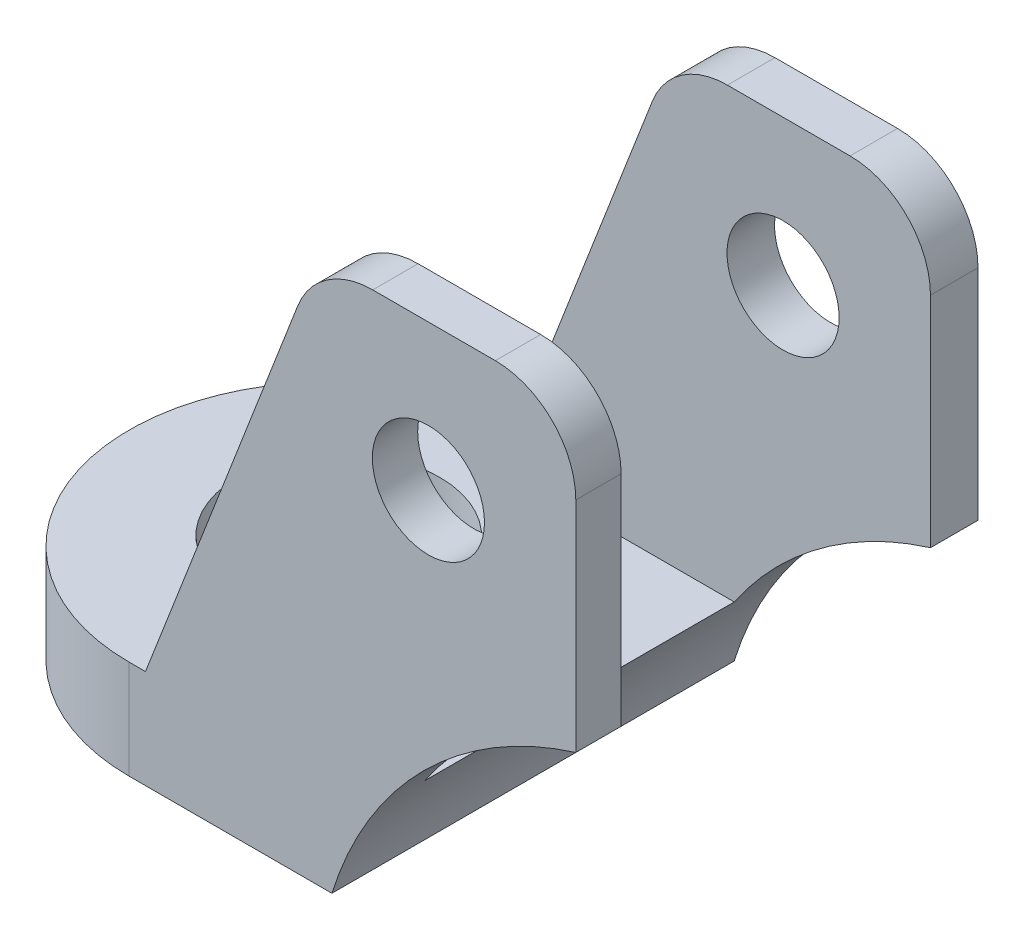
SolidWorks part; units mm, degrees
ref_plane "Front Plane" through (0, 0, 0) normal (0, 0, 1) x (1, 0, 0)
ref_plane "Top Plane" through (0, 0, 0) normal (0, 1, 0) x (1, 0, 0)
ref_plane "Right Plane" through (0, 0, 0) normal (1, 0, 0) x (0, 0, -1)
sketch "Sketch2" plane through (0, 0, 0) normal (0, 0, 1) x (1, 0, 0)
  line L0 (0, 0) -> (50.1973, 0)
  line L1 (80.5138, 30.3165) -> (80.5138, 67.5022)
  line L2 (80.5138, 67.5022) -> (48.4212, 67.5022)
  line L3 (48.4212, 67.5022) -> (27.0213, 12.2851)
  line L4 (27.0213, 12.2851) -> (0, 12.2851)
  line L5 (0, 12.2851) -> (0, 0)
  arc A1 (50.1973, 0) -> (80.5138, 30.3165) centre (94.1326, -13.6188) cw
  circle A2 centre (62.1924, 49.3996) radius 6.9687
extrude "Boss-Extrude1" add sketch "Sketch2" along normal mid plane 50
sketch "Sketch3" plane through (0, 0, 0) normal (1, 0, 0) x (0, 0, -1)
  line L0 (-25, 12.2851) -> (25, 12.2851) construction
  line L1 (19.0903, 12.2851) -> (-19.3656, 12.2851)
  line L2 (19.0903, 12.2851) -> (19.0903, 67.5022)
  line L3 (19.0903, 67.5022) -> (-19.3656, 67.5022)
  line L4 (-19.3656, 12.2851) -> (-19.3656, 67.5022)
  line L5 (-25, 67.5022) -> (25, 67.5022) construction
extrude "Cut-Extrude1" cut sketch "Sketch3" along normal through all
fillet "Fillet1" 2 edges at (0, 6.1426, 25) (0, 6.1426, -25) type full round first side face at (40.4171, 27.6628, 25) second side face at (40.4171, 27.6628, -25) middle face at (0, 6.1426, 0)
fillet "Fillet2" radius 10 1 edges at (48.4212, 67.5022, -22.0451) type face fillet first side face at (37.7213, 39.8936, -22.0451) second side face at (64.4675, 67.5022, -22.0451)
fillet "Fillet3" radius 10 1 edges at (80.5138, 67.5022, -22.0451) type face fillet first side face at (67.8921, 67.5022, -22.0451) second side face at (80.5138, 48.9093, -22.0451)
fillet "Fillet4" radius 10 1 edges at (48.4212, 67.5022, 22.1828) type face fillet first side face at (37.7213, 39.8936, 22.1828) second side face at (64.4675, 67.5022, 22.1828)
fillet "Fillet5" radius 10 1 edges at (80.5138, 67.5022, 22.1828) type face fillet first side face at (67.8921, 67.5022, 22.1828) second side face at (80.5138, 48.9093, 22.1828)
hole_wizard "3/4 NPT Tapped Hole1" positions "Sketch5" profile "Sketch6" size "3/4" standard "ANSI Inch" end condition through all
sketch "Sketch5" plane through (0, 12.2851, 0) normal (0, 1, 0) x (1, 0, 0)
  point P0 (24.3967, 1.6438)
sketch "Sketch6" plane through (24.3967, 12.2851, -1.6438) normal (1, 0, 0) x (0, 0, 1)
  line L0 (0, 0) -> (0, 12.2851)
  line L1 (0, 12.2851) -> (11.5062, 12.2851)
  line L2 (-12.1379, 14.05) -> (-12.5585, 0) construction
  line L3 (11.5062, 12.2851) -> (11.5062, 14.05)
  line L4 (11.5062, 14.05) -> (12.1379, 14.05)
  line L5 (12.1379, 14.05) -> (12.5585, 0)
  line L7 (12.5585, 0) -> (0, 0)
  line L8 (0, -6.35) -> (0, 107.95) construction
  line L11 (-11.5062, 14.05) -> (-12.1379, 14.05) construction
  dimension "Thru Tap Drill Dia." = 23.0124
  dimension "Thru Tap Drill Depth" = 12.2851
  dimension "Thread Dia." = 25.1171
  dimension "Thread Angle" = 3.43
  dimension "Thread Depth" = 14.05
cosmetic thread "Hole Thread1" parameters "D1"=14.05, "D2"=26.6698
